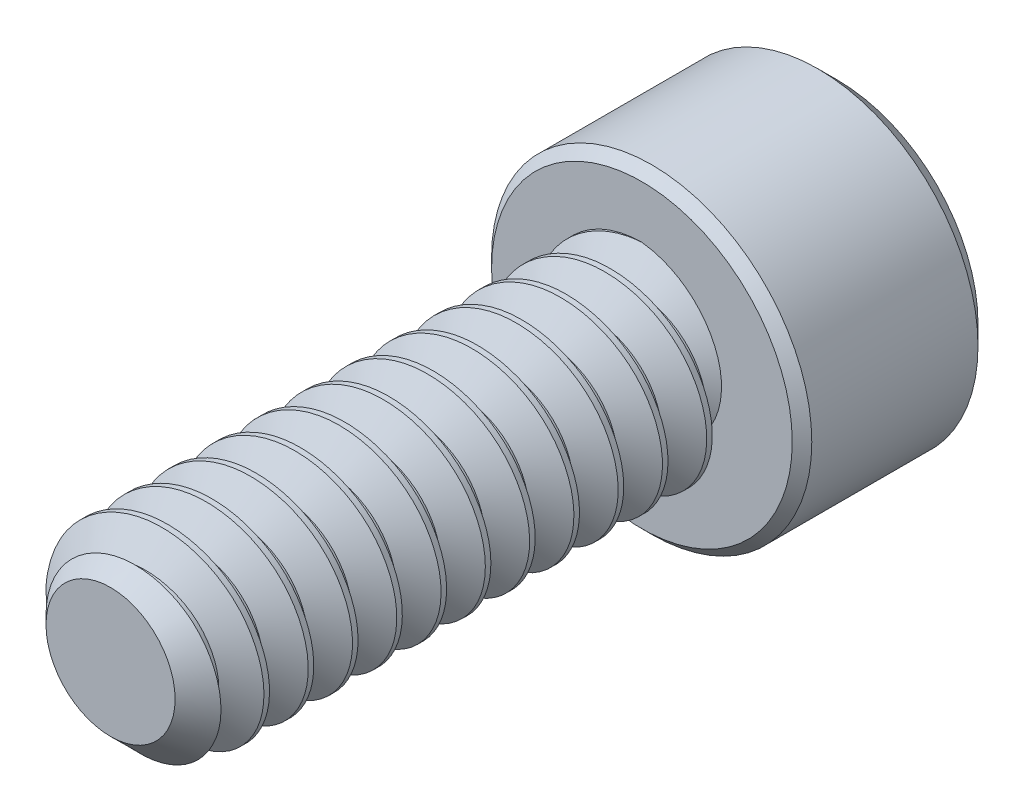
SolidWorks part; units mm, degrees
ref_plane "Front Plane" through (0, 0, 0) normal (0, 0, 1) x (1, 0, 0)
ref_plane "Top Plane" through (0, 0, 0) normal (0, 1, 0) x (1, 0, 0)
ref_plane "Right Plane" through (0, 0, 0) normal (1, 0, 0) x (0, 0, -1)
sketch "Sketch1" plane through (0, 0, 0) normal (0, 0, 1) x (1, 0, 0)
  line L0 (0, 1.7526) -> (0, -1.7526) construction
  circle A0 centre (0, 0) radius 1.7526
  dimension "OD" = 3.5052
extrude "Extrude1" add sketch "Sketch1" against normal blind 9.525
sketch "Sketch2" plane through (0, 0, 0) normal (0, 0, 1) x (1, 0, 0)
  circle A0 centre (0, 0) radius 1.7526 construction
  circle A1 centre (0, 0) radius 1.7526
curve "Helix/Spiral1" pitch 0.7937 height 10.3188 turns 13 parameters "pitch"=0.7937
chamfer "Chamfer3" distance 0.5953 angle 45 1 edges at (1.7526, 0, 0)
sketch "Sketch3" plane through (0, 0, 0) normal (1, 0, 0) x (0, 0, -1)
  line L0 (-0.6945, 1.7526) -> (-0.3969, 1.237)
  line L1 (-0.3969, 1.237) -> (-0.2977, 1.237)
  line L2 (-0.2977, 1.237) -> (0, 1.7526)
  line L3 (-0.6945, 1.7526) -> (0, 1.7526)
  line L4 (-0.3473, 1.7526) -> (-0.3473, 1.237) construction
  line L5 (-0.5457, 1.4948) -> (-0.1488, 1.4948) construction
  line L6 (0, 1.7526) -> (0, -1.7526) construction
  dimension "D1" = 0.0992
  dimension "D2" = 0.3969
  dimension "D3" = 60
sweep "Cut-Sweep1" cut profiles "Sketch3" path "Helix/Spiral1"
sketch "Sketch6" plane through (0, 0, -9.525) normal (0, 0, -1) x (-1, 0, 0)
  circle A0 centre (0, 0) radius 2.8702
  dimension "head dia" = 5.7404
extrude "Extrude2" add sketch "Sketch6" along normal blind 3.5052
sketch "Sketch7" plane through (0, 0, -13.0302) normal (0, 0, -1) x (-1, 0, 0)
  line L1 (0, 1.604) -> (-1.3891, 0.802)
  line L2 (-1.3891, 0.802) -> (-1.3891, -0.802)
  line L3 (-1.3891, -0.802) -> (0, -1.604)
  line L4 (0, -1.604) -> (1.3891, -0.802)
  line L5 (1.3891, -0.802) -> (1.3891, 0.802)
  line L6 (1.3891, 0.802) -> (0, 1.604)
  circle A0 centre (0, 0) radius 1.3891 construction
  dimension "hex dia" = 2.7781
extrude "Cut-Extrude1" cut sketch "Sketch7" against normal blind 2.0836
sketch "Sketch8" plane through (0, 0, -13.0302) normal (0, 0, -1) x (-1, 0, 0)
  circle A0 centre (0, 0) radius 1.604
extrude "Cut-Extrude2" cut sketch "Sketch8" against normal blind 0.3505 draft 45
chamfer "Chamfer1" distance 0.3505 angle 45 1 edges at (-2.8702, 0, -13.0302)
chamfer "Chamfer2" distance 0.1753 angle 45 1 edges at (-2.8702, 0, -9.525)
sketch "Sketch9" plane through (0, 0, 0) normal (1, 0, 0) x (0, 0, -1)
  line L0 (0, 1.7526) -> (0, -1.7526) construction
  line L1 (4.3656, 1.7526) -> (4.3656, -1.7526) construction
  line L2 (9.525, 2.8702) -> (9.525, -2.8702) construction
  line L3 (13.0302, 2.8702) -> (13.0302, -2.8702) construction
  line L4 (13.0302, 0) -> (0, 0) construction
  dimension "D1" = 4.3656
  dimension "D2" = 3.5052
  dimension "D3" = 5.7404
  dimension "D4" = 9.525
equation "\"D3@Helix/Spiral1\" = \"screw length@Extrude1\"+\"pitch@Helix/Spiral1\""
equation "\"D1@Sketch3\" = \"pitch@Helix/Spiral1\"*.125"
equation "\"D2@Sketch3\" = \"pitch@Helix/Spiral1\"*.5"
equation "\"D1@Cut-Extrude1\" = \"hex dia@Sketch7\"*.75"
equation "\"D1@Chamfer1\" = \"head depth@Extrude2\"/10"
equation "\"D1@Sketch9\" = \"pitch@Helix/Spiral1\"*5.5"
equation "\"D1@Chamfer2\" = \"D1@Chamfer1\"/2"
equation "\"D1@Cut-Extrude2\" = \"D1@Chamfer2\"*2"
equation "\"D1@Chamfer3\" = \"pitch@Helix/Spiral1\"*.750"
equation "\"D2@Sketch9\" = \"head depth@Extrude2\""
equation "\"D3@Sketch9\" = \"head dia@Sketch6\""
equation "\"D4@Sketch9\" = \"screw length@Extrude1\""
